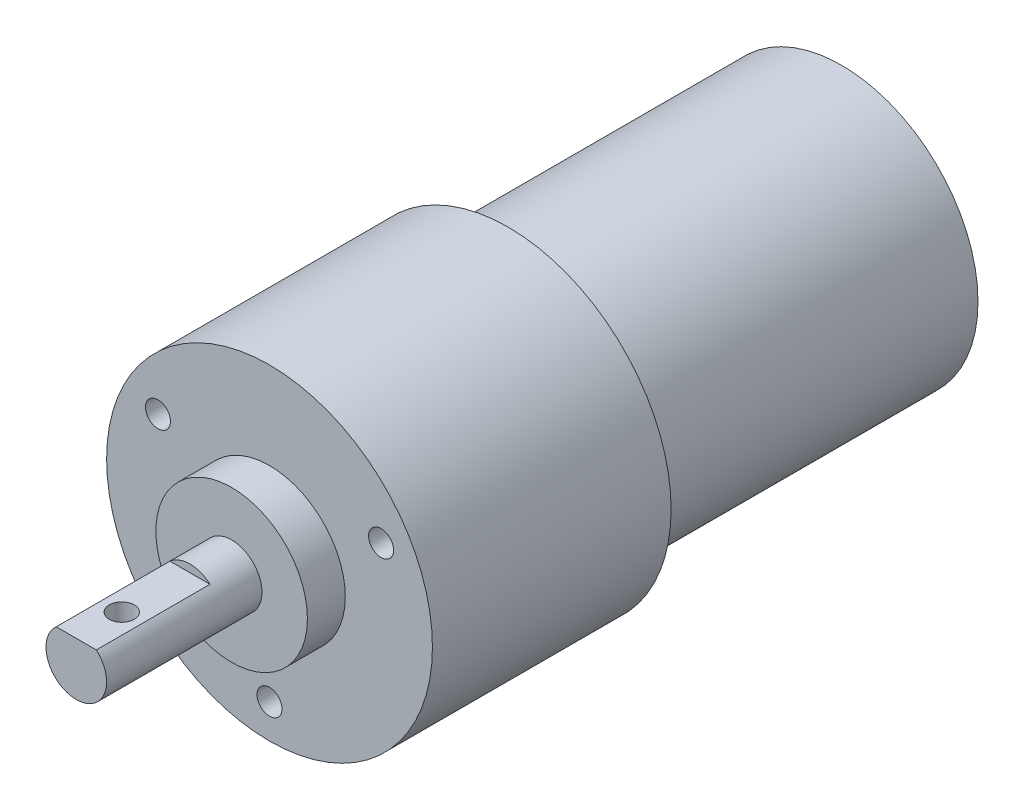
SolidWorks part; units mm, degrees
note: The reader was unsure of these and kept them because the rebuilt part matched: shared geometry of "ｽｹｯﾁ1<3>", "ｽｹｯﾁ2<2>".
material "AISI 1015 鋼, 冷間引抜 (SS)"
ref_plane "正面" through (0, 0, 0) normal (0, 0, 1) x (1, 0, 0)
ref_plane "平面" through (0, 0, 0) normal (0, 1, 0) x (1, 0, 0)
ref_plane "右側面" through (0, 0, 0) normal (1, 0, 0) x (0, 0, -1)
sketch "ｽｹｯﾁ1" plane through (0, 0, 0) normal (0, 0, 1) x (1, 0, 0)
  circle A0 centre (0, 0) radius 21.5
  circle A1 centre (0, 0) radius 18
  dimension "D1" = 43
  dimension "D2" = 36
extrude "ﾎﾞｽ - 押し出し1" add sketch "ｽｹｯﾁ1" along normal blind 31.5 contours A1 | A0 A1
extrude "ﾎﾞｽ - 押し出し2" add sketch "ｽｹｯﾁ1<3>" against normal blind 44 contours A1
sketch "ｽｹｯﾁ1<3>" plane through (0, 0, 0) normal (0, 0, 1) x (1, 0, 0) same geometry as "ｽｹｯﾁ1"
sketch "ｽｹｯﾁ2" plane through (0, 0, 31.5) normal (0, 0, 1) x (1, 0, 0)
  circle A0 centre (0, 0) radius 10
  circle A1 centre (0, 0) radius 4
  dimension "D1" = 20
  dimension "D2" = 8
extrude "ﾎﾞｽ - 押し出し3" add sketch "ｽｹｯﾁ2" along normal blind 5
extrude "ﾎﾞｽ - 押し出し4" add sketch "ｽｹｯﾁ2<2>" along normal blind 25.5 contours A1
sketch "ｽｹｯﾁ2<2>" plane through (0, 0, 31.5) normal (0, 0, 1) x (1, 0, 0) same geometry as "ｽｹｯﾁ2"
sketch "ｽｹｯﾁ3" plane through (0, 0, 0) normal (0, 1, 0) x (1, 0, 0)
  line L0 (0, -23.65) -> (0, 23.65) construction
  line L1 (-7.9531, -42) -> (7.9531, -42)
  line L2 (-7.9531, -42) -> (-7.9531, -57)
  line L3 (-7.9531, -57) -> (7.9531, -57)
  line L4 (7.9531, -42) -> (7.9531, -57)
  line L5 (-7.9531, -42) -> (7.9531, -57) construction
  line L6 (-7.9531, -57) -> (7.9531, -42) construction
  line L7 (-4, -57) -> (4, -57) construction
  point P0 (0, -49.5)
  dimension "D1" = 15
extrude "ｶｯﾄ - 押し出し1" cut sketch "ｽｹｯﾁ3" along normal through all from offset 3
hole_wizard "M4x0.7 ねじ穴1" positions "ｽｹｯﾁ4" profile "ｽｹｯﾁ5" tap size "M4x0.7" standard "JIS"
sketch "ｽｹｯﾁ4" plane through (0, 0, 31.5) normal (0, 0, 1) x (1, 0, 0)
  line L0 (0, -17) -> (0, 0) construction
  circle A0 centre (0, 0) radius 17 construction
  point P0 (0, -17)
  point P18 (-14.7224, 8.5)
  point P19 (14.7224, 8.5)
  point P21 (0, 0)
  dimension "D1" = 34
  dimension "D3" = 3
sketch "ｽｹｯﾁ5" plane through (0, -17, 31.5) normal (1, 0, 0) x (0, -1, 0)
  line L0 (0, 0) -> (0, 12.4914)
  line L1 (0, 12.4914) -> (1.65, 11.5)
  line L2 (1.65, 11.5) -> (1.65, 0)
  line L5 (1.65, 0) -> (0, 0)
  line L10 (0, 12.4914) -> (-1.65, 11.5) construction
  line L11 (0, -6.35) -> (0, 107.95) construction
  dimension "ねじ下穴ﾄﾞﾘﾙ直径" = 3.3
  dimension "ねじ下穴ﾄﾞﾘﾙの深さ" = 11.5
  dimension "ﾄﾞﾘﾙ角度" = 118
cosmetic thread "穴のねじ山2" parameters "D1"=8, "D2"=4
cosmetic thread "穴のねじ山3" parameters "D1"=8, "D2"=4
cosmetic thread "穴のねじ山4" parameters "D1"=8, "D2"=4
hole_wizard "M4x0.7 ねじ穴2" positions "ｽｹｯﾁ6" profile "ｽｹｯﾁ7" tap size "M4x0.7" standard "JIS" end condition through all
sketch "ｽｹｯﾁ6" plane through (0, 3, 0) normal (0, 1, 0) x (1, 0, 0)
  line L0 (2.6458, -57) -> (-2.6458, -57) construction
  line L1 (0, -23.65) -> (0, 23.65) construction
  point P0 (0, -51)
  dimension "D1" = 6
sketch "ｽｹｯﾁ7" plane through (0, 3, 51) normal (1, 0, 0) x (0, 0, 1)
  line L0 (0, 0) -> (0, 24.5)
  line L1 (0, 24.5) -> (1.65, 24.5)
  line L2 (1.65, 24.5) -> (1.65, 0)
  line L5 (1.65, 0) -> (0, 0)
  line L11 (0, -6.35) -> (0, 107.95) construction
  dimension "次ｻｰﾌｪｽまでのねじ下穴ﾄﾞﾘﾙ直径" = 3.3
  dimension "次ｻｰﾌｪｽまでのねじ下穴ﾄﾞﾘﾙの深さ" = 24.5
cosmetic thread "穴のねじ山5" parameters "D2"=4
